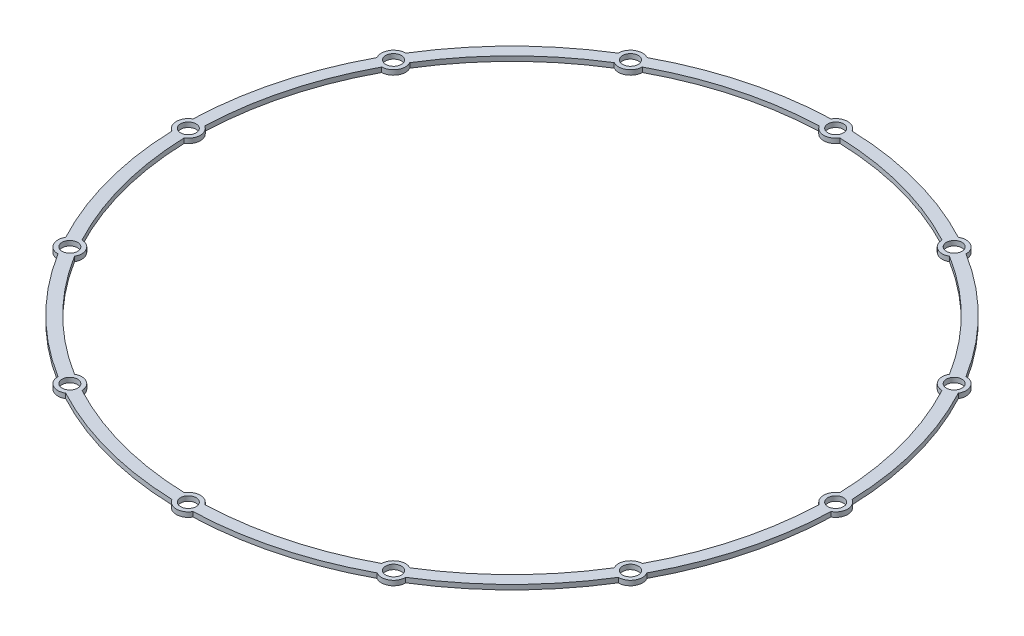
SolidWorks part; units mm, degrees
material "6061 Alloy"
ref_plane "Front Plane" through (0, 0, 0) normal (0, 0, 1) x (1, 0, 0)
ref_plane "Top Plane" through (0, 0, 0) normal (0, 1, 0) x (1, 0, 0)
ref_plane "Right Plane" through (0, 0, 0) normal (1, 0, 0) x (0, 0, -1)
sketch "Sketch1" plane through (0, 0, 0) normal (0, 1, 0) x (1, 0, 0)
  circle A0 centre (0, 0) radius 68.58 construction
  circle A1 centre (0, 0) radius 69.85
  circle A2 centre (0, 0) radius 67.31
  circle A3 centre (0, 0) radius 71.12
  circle A4 centre (0, 0) radius 66.04
  circle A5 centre (0, -68.58) radius 1.651
  circle A6 centre (0, -68.58) radius 2.54
  dimension "D1" = 137.16
  dimension "D6" = 3.302
  dimension "D2" = 1.27
  dimension "D3" = 1.27
  dimension "D4" = 2.54
  dimension "D5" = 2.54
extrude "Boss-Extrude1" add sketch "Sketch1" along normal blind 1.016 contours A6 A1 A2 | A2 A6 A1 A5 | A1 A5 A2 | A1 A6 A2 A5 region at (48.7512, 0, 47.2258) region at (-1.9394, 0, 68.556) region at (1.9394, 0, 68.556) region at (0, 0, 68.5781)
extrude "Boss-Extrude2" add sketch "Sketch1<3>" along normal blind 1.016 contours A2 A6 A5 | A6 A1 A5 region at (0, 0, 70.422) region at (0, 0, 66.7224)
sketch "Sketch1<3>" plane through (0, 0, 0) normal (0, 1, 0) x (1, 0, 0) same geometry as "Sketch1"
extrude "Cut-Extrude1" cut sketch "Sketch1<4>" along normal up to surface (1.016 mm away) contours A1 A5 | A2 A5 | A1 A5 A2 region at (0, 0, 68.5781) region at (0, 0, 70.0024) region at (0, 0, 67.1544) up to face at (0, 1.016, 0.635)
sketch "Sketch1<4>" plane through (0, 0, 0) normal (0, 1, 0) x (1, 0, 0) same geometry as "Sketch1"
pattern_circular "CirPattern2" count 12 over 360 about axis through (0, 1.016, 0) along (0, 1, 0) of "Cut-Extrude1", "Boss-Extrude2"
ref_plane "Plane1" through (0, 0.508, 0) normal (0, 1, 0) x (1, 0, 0)
sketch "Sketch2" plane through (0, 0.508, 0) normal (0, 1, 0) x (1, 0, 0)
  circle A0 centre (-59.392, 34.29) radius 1.651 construction
  circle A1 centre (-34.29, 59.392) radius 1.651 construction
  circle A2 centre (-68.58, 0) radius 1.651 construction
  circle A3 centre (-59.392, -34.29) radius 1.651 construction
  circle A4 centre (-34.29, -59.392) radius 1.651 construction
  circle A5 centre (0, -68.58) radius 1.651 construction
  circle A6 centre (34.29, -59.392) radius 1.651 construction
  circle A7 centre (59.392, -34.29) radius 1.651 construction
  circle A8 centre (68.58, 0) radius 1.651 construction
  circle A9 centre (59.392, 34.29) radius 1.651 construction
  circle A10 centre (34.29, 59.392) radius 1.651 construction
  circle A11 centre (0, 68.58) radius 1.651 construction
  circle A12 centre (-59.392, 34.29) radius 1.651
  circle A13 centre (-68.58, 0) radius 1.651
  circle A14 centre (-59.392, -34.29) radius 1.651
  circle A15 centre (-34.29, -59.392) radius 1.651
  circle A16 centre (0, -68.58) radius 1.651
  circle A17 centre (34.29, -59.392) radius 1.651
  circle A18 centre (59.392, -34.29) radius 1.651
  circle A19 centre (68.58, 0) radius 1.651
  circle A20 centre (59.392, 34.29) radius 1.651
  circle A21 centre (34.29, 59.392) radius 1.651
  circle A22 centre (0, 68.58) radius 1.651
  circle A23 centre (-34.29, 59.392) radius 1.651
  arc A24 (-36.8297, -59.3515) -> (-32.985, -61.5712) centre (-34.29, -59.392) ccw
  arc A25 (-32.985, -61.5712) -> (-2.2197, -69.8147) centre (0, 0) ccw
  arc A26 (-2.2197, -69.8147) -> (2.2197, -69.8147) centre (0, -68.58) ccw
  arc A27 (2.2197, -69.8147) -> (32.985, -61.5712) centre (0, 0) ccw
  arc A28 (32.985, -61.5712) -> (36.8297, -59.3515) centre (34.29, -59.392) ccw
  arc A29 (36.8297, -59.3515) -> (59.3515, -36.8297) centre (0, 0) ccw
  arc A30 (59.3515, -36.8297) -> (61.5712, -32.985) centre (59.392, -34.29) ccw
  arc A31 (61.5712, -32.985) -> (69.8147, -2.2197) centre (0, 0) ccw
  arc A32 (69.8147, -2.2197) -> (69.8147, 2.2197) centre (68.58, 0) ccw
  arc A33 (69.8147, 2.2197) -> (61.5712, 32.985) centre (0, 0) ccw
  arc A34 (61.5712, 32.985) -> (59.3515, 36.8297) centre (59.392, 34.29) ccw
  arc A35 (59.3515, 36.8297) -> (36.8297, 59.3515) centre (0, 0) ccw
  arc A36 (36.8297, 59.3515) -> (32.985, 61.5712) centre (34.29, 59.392) ccw
  arc A37 (32.985, 61.5712) -> (2.2197, 69.8147) centre (0, 0) ccw
  arc A38 (2.2197, 69.8147) -> (-2.2197, 69.8147) centre (0, 68.58) ccw
  arc A39 (-2.2197, 69.8147) -> (-32.985, 61.5712) centre (0, 0) ccw
  arc A40 (-32.985, 61.5712) -> (-36.8297, 59.3515) centre (-34.29, 59.392) ccw
  arc A41 (-36.8297, 59.3515) -> (-59.3515, 36.8297) centre (0, 0) ccw
  arc A42 (-59.3515, 36.8297) -> (-61.5712, 32.985) centre (-59.392, 34.29) ccw
  arc A43 (-61.5712, 32.985) -> (-69.8147, 2.2197) centre (0, 0) ccw
  arc A44 (-69.8147, 2.2197) -> (-69.8147, -2.2197) centre (-68.58, 0) ccw
  arc A45 (-69.8147, -2.2197) -> (-61.5712, -32.985) centre (0, 0) ccw
  arc A46 (-61.5712, -32.985) -> (-59.3515, -36.8297) centre (-59.392, -34.29) ccw
  arc A47 (-59.3515, -36.8297) -> (-36.8297, -59.3515) centre (0, 0) ccw
  arc A48 (-36.8297, -59.3515) -> (-32.985, -61.5712) centre (-34.29, -59.392) ccw
  arc A49 (-32.985, -61.5712) -> (-2.2197, -69.8147) centre (0, 0) ccw
  arc A50 (-2.2197, -69.8147) -> (2.2197, -69.8147) centre (0, -68.58) ccw
  arc A51 (2.2197, -69.8147) -> (32.985, -61.5712) centre (0, 0) ccw
  arc A52 (32.985, -61.5712) -> (36.8297, -59.3515) centre (34.29, -59.392) ccw
  arc A53 (36.8297, -59.3515) -> (59.3515, -36.8297) centre (0, 0) ccw
  arc A54 (59.3515, -36.8297) -> (61.5712, -32.985) centre (59.392, -34.29) ccw
  arc A55 (61.5712, -32.985) -> (69.8147, -2.2197) centre (0, 0) ccw
  arc A56 (69.8147, -2.2197) -> (69.8147, 2.2197) centre (68.58, 0) ccw
  arc A57 (69.8147, 2.2197) -> (61.5712, 32.985) centre (0, 0) ccw
  arc A58 (61.5712, 32.985) -> (59.3515, 36.8297) centre (59.392, 34.29) ccw
  arc A59 (59.3515, 36.8297) -> (36.8297, 59.3515) centre (0, 0) ccw
  arc A60 (36.8297, 59.3515) -> (32.985, 61.5712) centre (34.29, 59.392) ccw
  arc A61 (32.985, 61.5712) -> (2.2197, 69.8147) centre (0, 0) ccw
  arc A62 (2.2197, 69.8147) -> (-2.2197, 69.8147) centre (0, 68.58) ccw
  arc A63 (-2.2197, 69.8147) -> (-32.985, 61.5712) centre (0, 0) ccw
  arc A64 (-32.985, 61.5712) -> (-36.8297, 59.3515) centre (-34.29, 59.392) ccw
  arc A65 (-36.8297, 59.3515) -> (-59.3515, 36.8297) centre (0, 0) ccw
  arc A66 (-59.3515, 36.8297) -> (-61.5712, 32.985) centre (-59.392, 34.29) ccw
  arc A67 (-61.5712, 32.985) -> (-69.8147, 2.2197) centre (0, 0) ccw
  arc A68 (-69.8147, 2.2197) -> (-69.8147, -2.2197) centre (-68.58, 0) ccw
  arc A69 (-69.8147, -2.2197) -> (-61.5712, -32.985) centre (0, 0) ccw
  arc A70 (-61.5712, -32.985) -> (-59.3515, -36.8297) centre (-59.392, -34.29) ccw
  arc A71 (-59.3515, -36.8297) -> (-36.8297, -59.3515) centre (0, 0) ccw
  dimension "D1" = 0
equation "\"Middle Coupler Inner Daimeter\"= 4.5in"
equation "\"Middle Coupler  Wall Thickness\" = 0.25in"
equation "\"Middle Coupler Bottom Thickness\"= 0.2in"
equation "\"Bearing Rail Offset\"= 0.45in"
equation "\"3-56 UNF Tap\"= 0.089in"
equation "\"3-56 UNF Clearance\"= 0.104in"
equation "\"Ball Bearing Distance\"= 0.03in"
equation "\"TCA Outer Diameter\" = 6.625in"
equation "\"D1@Sketch1\"=\"Middle Coupler Inner Daimeter\"+\"Bearing Rail Offset\"*2in"
equation "\"Interstage Aeroframe Wall Thickness\" = 0.072in"
equation "\"Compression Spring OD\"= 0.42in"
equation "\"10-24 Tap\"= 0.157in"
equation "\"10-24 Clearance\"= 0.196in"
equation "\"Lower Stage Fuselage Wall Thickness\" = 0.25in"
equation "\"6-32 Tap\" = 0.107in"
equation "\"1/4-20 Tap\" = 0.201in"
